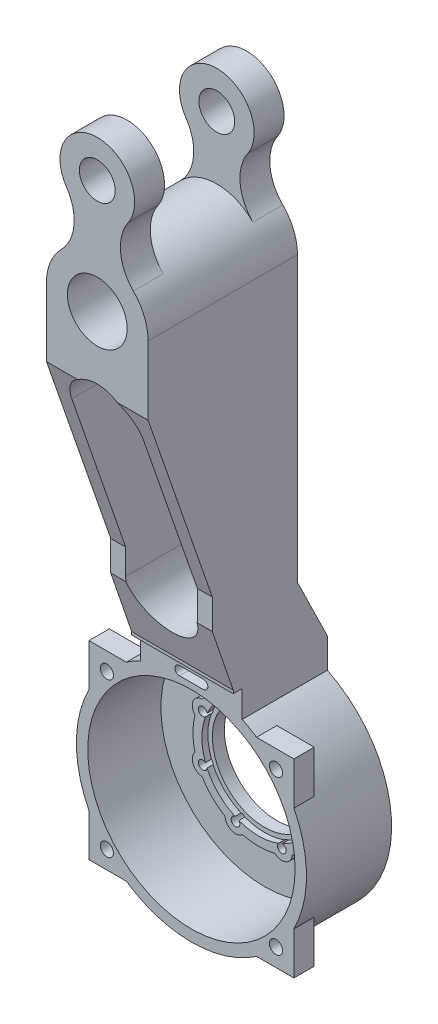
SolidWorks part; units mm, degrees
material "ABS"
ref_plane "Front Plane" through (0, 0, 0) normal (0, 0, 1) x (1, 0, 0)
ref_plane "Top Plane" through (0, 0, 0) normal (0, 1, 0) x (1, 0, 0)
ref_plane "Right Plane" through (0, 0, 0) normal (1, 0, 0) x (0, 0, -1)
sketch "Sketch1" plane through (0, 0, 0) normal (0, 0, 1) x (1, 0, 0)
  line L0 (0, 55.6228) -> (0, -56.75) construction
  line L1 (-58.5265, 0) -> (65.4088, 0) construction
  line L2 (-17, 34.5435) -> (-17, 43.5)
  line L3 (-17, 43.5) -> (17, 43.5)
  line L4 (17, 43.5) -> (17, 34.5435)
  circle A0 centre (0, 0) radius 33.5 construction
  circle A1 centre (0, 0) radius 34.7
  arc A2 (-17, 34.5435) -> (17, 34.5435) centre (0, 0) ccw
  circle A4 centre (0, 0) radius 20.25 construction
  circle A7 centre (0, 0) radius 17.5
  circle A8 centre (-7.7493, 18.7086) radius 1.45
  circle A9 centre (7.7493, 18.7086) radius 1.45
  circle A10 centre (18.7086, 7.7493) radius 1.45
  circle A11 centre (18.7086, -7.7493) radius 1.45
  circle A12 centre (7.7493, -18.7086) radius 1.45
  circle A13 centre (-7.7493, -18.7086) radius 1.45
  circle A14 centre (-18.7086, -7.7493) radius 1.45
  circle A15 centre (-18.7086, 7.7493) radius 1.45
  point P32 (0, 0)
  dimension "D1" = 67
  dimension "D7" = 40.5
  dimension "D10" = 35
  dimension "D6" = 2.9
  dimension "D9" = 38.5
  dimension "D2" = 5
  dimension "D3" = 1.2
  dimension "D4" = 34
  dimension "D5" = 10
  dimension "D8" = 8
extrude "FrontPanel" add sketch "Sketch1" along normal blind 4 contours L2 A2 L4 L3 A1 | A1 A15 A14 A13 A12 A11 A10 A9 A8 A7 region at (-15.8751, 39.0217, 0) region at (-33.7185, 0, 0)
extrude "SideWalls" add sketch "Sketch1<3>" along normal blind 28.5 contours L2 A2 L4 L3 A1 region at (-15.8751, 39.0217, 0)
sketch "Sketch1<3>" plane through (0, 0, 0) normal (0, 0, 1) x (1, 0, 0) same geometry as "Sketch1"
sketch "Sketch2" plane through (0, 0, 4) normal (0, 0, 1) x (1, 0, 0)
  arc A0 (-5.4209, 21.3217) -> (-11.2435, 18.9099) centre (-7.7493, 18.7086) ccw
  circle A1 centre (0, 0) radius 20.25 construction
  circle A2 centre (0, 0) radius 19
  arc A3 (-11.2435, 18.9099) -> (-18.9099, 11.2435) centre (0, 0) ccw
  arc A4 (11.2435, 18.9099) -> (5.4209, 21.3217) centre (7.7493, 18.7086) ccw
  arc A5 (21.3217, 5.4209) -> (18.9099, 11.2435) centre (18.7086, 7.7493) ccw
  arc A6 (18.9099, -11.2435) -> (21.3217, -5.4209) centre (18.7086, -7.7493) ccw
  arc A7 (5.4209, -21.3217) -> (11.2435, -18.9099) centre (7.7493, -18.7086) ccw
  arc A8 (-11.2435, -18.9099) -> (-5.4209, -21.3217) centre (-7.7493, -18.7086) ccw
  arc A9 (-21.3217, -5.4209) -> (-18.9099, -11.2435) centre (-18.7086, -7.7493) ccw
  arc A10 (-18.9099, 11.2435) -> (-21.3217, 5.4209) centre (-18.7086, 7.7493) ccw
  arc A11 (5.4209, 21.3217) -> (-5.4209, 21.3217) centre (0, 0) ccw
  arc A12 (18.9099, 11.2435) -> (11.2435, 18.9099) centre (0, 0) ccw
  arc A13 (21.3217, -5.4209) -> (21.3217, 5.4209) centre (0, 0) ccw
  arc A14 (11.2435, -18.9099) -> (18.9099, -11.2435) centre (0, 0) ccw
  arc A15 (-5.4209, -21.3217) -> (5.4209, -21.3217) centre (0, 0) ccw
  arc A16 (-18.9099, -11.2435) -> (-11.2435, -18.9099) centre (0, 0) ccw
  arc A17 (-21.3217, 5.4209) -> (-21.3217, -5.4209) centre (0, 0) ccw
  point P32 (0, 0)
  dimension "D1" = 7
  dimension "D2" = 38
  dimension "D3" = 3
  dimension "D4" = 8
extrude "MotorSpacer" add sketch "Sketch2" along normal blind 2
extrude "MotorMountingHoles" cut sketch "Sketch1<5>" along normal blind 6 contours A15 | A14 | A13 | A12 | A11 | A10 | A9 | A8
sketch "Sketch1<5>" plane through (0, 0, 0) normal (0, 0, 1) x (1, 0, 0) same geometry as "Sketch1"
sketch "Sketch3" plane through (0, 0, 28.5) normal (0, 0, 1) x (1, 0, 0)
  line L0 (-58.5265, 0) -> (65.4088, 0) construction
  line L1 (0, 55.6228) -> (0, -56.75) construction
  line L2 (0, 51.8514) -> (0, -45.3103) construction
  line L3 (-50.1667, 0) -> (45.3988, 0) construction
  line L4 (-34.3, 31.75) -> (-21.7758, 31.75)
  line L5 (34.3, 31.75) -> (21.7758, 31.75)
  line L7 (34.3, 31.75) -> (34.3, 17.486)
  line L8 (-34.3, 31.75) -> (-34.3, 17.486)
  line L9 (-34.3, -31.75) -> (-21.7758, -31.75)
  line L10 (-34.3, -31.75) -> (-34.3, -17.486)
  line L11 (34.3, -31.75) -> (21.7758, -31.75)
  line L12 (34.3, -31.75) -> (34.3, -17.486)
  circle A18 centre (-28.3, 25.75) radius 2.2
  arc A45 (21.7758, 31.75) -> (34.3, 17.486) centre (0, 0) cw
  arc A47 (-17, 34.5435) -> (17, 34.5435) centre (0, 0) ccw construction
  circle A48 centre (28.3, 25.75) radius 2.2
  arc A49 (-21.7758, 31.75) -> (-34.3, 17.486) centre (0, 0) ccw
  arc A50 (-21.7758, -31.75) -> (-34.3, -17.486) centre (0, 0) cw
  circle A51 centre (-28.3, -25.75) radius 2.2
  circle A52 centre (28.3, -25.75) radius 2.2
  arc A53 (21.7758, -31.75) -> (34.3, -17.486) centre (0, 0) ccw
  arc M14 (-17, 34.5435) -> (17, 34.5435) centre (0, 0) ccw
  dimension "D3" = 4.4
  dimension "D4" = 6
  dimension "D5" = 6
  dimension "D1" = 28.3
  dimension "D2" = 25.75
extrude "Boss-Extrude7" add sketch "Sketch3" against normal blind 6.8 contours A18 L4 L8 M14 | A48 L7 L5 M14 | A52 L11 L12 M14 | A51 L10 L9 M14 | A18 | A51 | A52 | A48 region at (30.6142, 27.5086, 28.5) region at (30.6142, -27.5086, 28.5) region at (-30.6142, -27.5086, 28.5) region at (-30.6142, 27.5086, 28.5)
extrude "Cut-Extrude2" cut sketch "Sketch3<5>" against normal blind 6 contours A18 | A48 | A52 | A51
sketch "Sketch3<5>" plane through (0, 0, 28.5) normal (0, 0, 1) x (1, 0, 0) same geometry as "Sketch3"
sketch "Sketch7" plane through (0, 0, 28.5) normal (0, 0, 1) x (1, 0, 0)
  line L0 (-4, 38.2) -> (4, 38.2) construction
  line L5 (0, 51.8514) -> (0, -45.3103) construction
  line L6 (-4, 39.7) -> (4, 39.7)
  line L7 (-4, 36.7) -> (4, 36.7)
  arc A7 (-4, 39.7) -> (-4, 36.7) centre (-4, 38.2) ccw
  arc A8 (4, 36.7) -> (4, 39.7) centre (4, 38.2) ccw
  circle A13 centre (0, 0) radius 34.7 construction
  point P4 (0, 38.2)
  dimension "D4" = 11
  dimension "D1" = 3
  dimension "D2" = 8
  dimension "D3" = 2
ref_plane "Plane2" through (0, 34.7, 0) normal (0, -1, 0) x (-1, 0, 0)
sketch "Sketch9" plane through (0, 34.7, 0) normal (0, -1, 0) x (-1, 0, 0)
  line L0 (38.5, 0) -> (-38.5, 0) construction
  line L1 (-6.5, 0) -> (6.5, 0)
  line L2 (-6.5, -3.2) -> (-6.5, -8)
  line L3 (-6.5, -8) -> (6.5, -8)
  line L4 (6.5, -3.2) -> (6.5, -8)
  line L5 (-6.5, -3.2) -> (-8, -3.2)
  line L6 (-8, -3.2) -> (-6.5, 0)
  line L7 (-11.2435, -4) -> (-5.4209, -4) construction
  line L10 (0, 6.8938) -> (0, -12.2231) construction
  line L11 (6.5, 0) -> (8, -3.2)
  line L12 (8, -3.2) -> (6.5, -3.2)
  point P0 (0, -4)
  dimension "D1" = 13
  dimension "D2" = 4
  dimension "D3" = 1.5
  dimension "D4" = 3.2
  dimension "D5" = 13
extrude "Cut-Extrude8" cut sketch "Sketch7" against normal through all
ref_plane "Plane3" through (0, 0, 5) normal (0, 0, -1) x (-1, 0, 0)
sketch "Sketch10" plane through (0, 0, 5) normal (0, 0, -1) x (-1, 0, 0)
  circle A0 centre (0, 0) radius 62 construction
  dimension "D1" = 124
ref_plane "Plane4" through (0, 65, 0) normal (0, 1, 0) x (1, 0, 0)
sketch "Sketch11" plane through (0, 65, 0) normal (0, 1, 0) x (1, 0, 0)
  line L0 (-17, -28.5) -> (-17, 0) construction
  line L5 (-17, -10) -> (17, -10)
  line L6 (-17, -10) -> (-17, -38.5)
  line L7 (-17, -38.5) -> (17, -38.5)
  line L8 (17, -10) -> (17, -38.5)
  line L9 (62, -5) -> (-62, -5) construction
  line L10 (-17, -28.5) -> (-17, 0) construction
  line L11 (17, -28.5) -> (17, 0) construction
  dimension "D1" = 5
extrude "Boss-Extrude8" add sketch "Sketch11" along normal blind 10 separate body
sketch "Sketch14" plane through (0, 43.5, 0) normal (0, 1, 0) x (1, 0, 0)
  line L0 (17, -38.5) -> (17, -10) construction
  line L1 (-17, 0) -> (17, 0)
  line L2 (-17, 0) -> (-17, -31.5)
  line L3 (-17, -31.5) -> (17, -31.5)
  line L4 (17, 0) -> (17, -31.5)
  line L5 (17, -28.5) -> (21.7758, -28.5) construction
  dimension "D1" = 3
extrude "Boss-Extrude9" add sketch "Sketch14" along normal blind 1 contours L2 L3 L4 L1
loft "Loft5" add section face at (0, 44.5, 15.75) section face at (0, 65, 24.25) connector at (17, 44.5, 31.5) connector at (17, 65, 38.5)
extrude "Cut-Extrude11" cut sketch "Sketch9" against normal blind 16 and the other way blind 1
sketch "Sketch16" plane through (0, 0, 0) normal (0, 0, 1) x (1, 0, 0)
  line L0 (0, 0) -> (0, 356.2393)
  line L1 (0, 356.2393) -> (166.2695, 342.3584)
  line L2 (0, 265.2066) -> (215.9891, 255.0325)
  line L3 (201.3656, 509.4722) -> (94.5843, 342.3584)
  line L4 (94.5843, 342.3584) -> (262.4153, 186.8493)
  line L5 (262.4153, 186.8493) -> (312.0984, 264.6038)
  line L6 (312.0984, 264.6038) -> (201.3656, 509.4722)
  circle A0 centre (0, 0) radius 100
  dimension "D1" = 200
sketch "Sketch19" plane through (0, 0, 10) normal (0, 0, -1) x (-1, 0, 0)
  line L2 (-17, 75) -> (17, 75)
  line L3 (-17, 75) -> (-17, 160)
  line L4 (17, 160) -> (17, 75)
  line L5 (0, 198) -> (0, 160) construction
  line L7 (-17, 143) -> (17, 143) construction
  line L12 (0, 127) -> (0, 66.5) construction
  line L13 (12, 127) -> (12, 66.5)
  line L14 (-12, 127) -> (-12, 66.5)
  line L15 (17, 44.5) -> (-17, 44.5) construction
  arc A5 (-17, 160) -> (-12.076, 171.9654) centre (0, 160) cw
  circle A6 centre (0, 198) radius 6
  arc A7 (10.3324, 190.965) -> (-10.3324, 190.965) centre (0, 198) ccw
  circle A8 centre (0, 160) radius 10
  arc A10 (10.3324, 190.965) -> (12.076, 171.9654) centre (22.7313, 182.523) ccw
  arc A11 (-10.3324, 190.965) -> (-12.076, 171.9654) centre (-22.7313, 182.523) cw
  arc A12 (12.076, 171.9654) -> (17, 160) centre (0, 160) cw
  circle A13 centre (0, 160) radius 17 construction
  arc A15 (-12.076, 171.9654) -> (12.076, 171.9654) centre (0, 160) cw
  arc A19 (-17, 34.5435) -> (17, 34.5435) centre (0, 0) ccw construction
  arc A20 (12, 127) -> (-12, 127) centre (0, 127) ccw
  arc A21 (-12, 66.5) -> (12, 66.5) centre (0, 66.5) ccw
  point P27 (0, -38.5)
  point P30 (0, 96.75)
  point P35 (0, 54.5)
  line M3 (-17, 65) -> (17, 65)
  dimension "D1" = 20
  dimension "D4" = 25
  dimension "D5" = 12
  dimension "D6" = 30
  dimension "D7" = 17
  dimension "D8" = 4
  dimension "D9" = 249
  dimension "D2" = 160
  dimension "D3" = 38
  dimension "D10" = 5
  dimension "D11" = 10
extrude "Boss-Extrude10" add sketch "Sketch19" against normal blind 50 contours A8 | A6 | A6 | L4 L2 L3 A5 A11 A7 A10 A12 region at (0, 198, 10) region at (0, 160, 10)
sketch "Sketch21" plane through (17, 0, 0) normal (1, 0, 0) x (0, 0, -1)
  line L0 (-38.5, 75) -> (-60, 75)
  line L1 (-60, 75) -> (-60, 137)
  line L2 (-60, 75) -> (-60, 160) construction
  line L3 (-60, 137) -> (-38.5, 75)
  line L6 (-10, 143) -> (-60, 143) construction
  dimension "D1" = 6
  dimension "D2" = 62
extrude "Cut-Extrude12" cut sketch "Sketch21" against normal up to next contours L3 L0 L1
extrude "Cut-Extrude14" cut sketch "Sketch19<5>" against normal through all from offset 5 contours L13 A20 L14 L2 | L14 A21 L13 L2 M3 | A21 M3 region at (0, 105.7708, 10) region at (0, 70.0018, 10) region at (0, 60.5874, 10) offset against normal yes
sketch "Sketch19<5>" plane through (0, 0, 10) normal (0, 0, -1) x (-1, 0, 0) same geometry as "Sketch19"
extrude "Cut-Extrude15" cut sketch "Sketch19<6>" against normal offset from surface (30 mm away) 10 from offset 10 contours A11 A15 A10 A7 A6 region at (7.3367, 181.1103, 10) up to face at (-6, 198, 60) offset against normal yes
sketch "Sketch19<6>" plane through (0, 0, 10) normal (0, 0, -1) x (-1, 0, 0) same geometry as "Sketch19"
equation "\"MotorDismetr\"= 67"
equation "\"D1@Sketch1\"=\"MotorDismetr\""
equation "\"M3ForThread\"=4"
